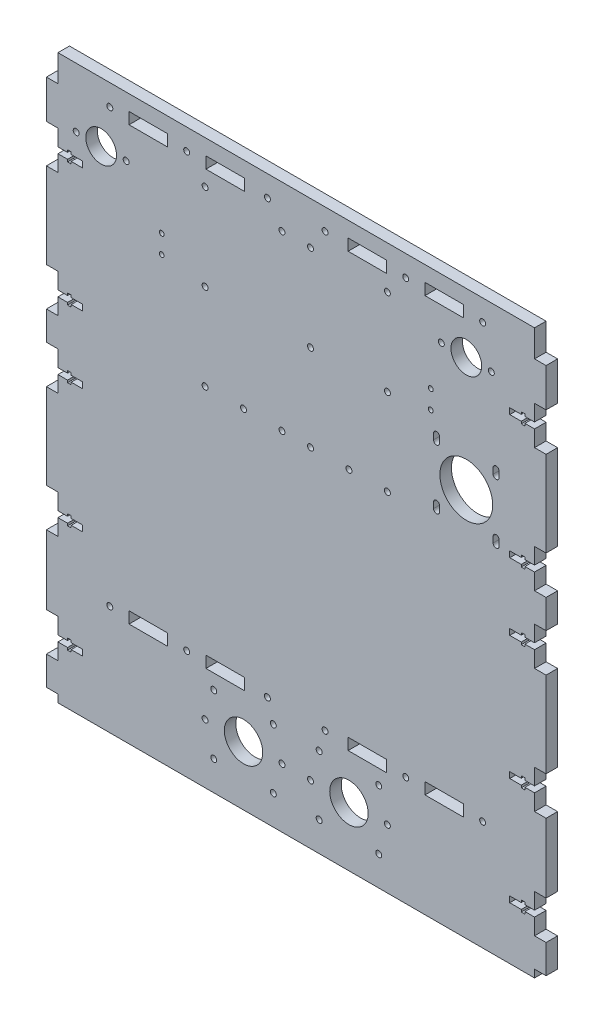
SolidWorks part; units mm, degrees
ref_plane "Front Plane" through (0, 0, 0) normal (0, 0, 1) x (1, 0, 0)
ref_plane "Top Plane" through (0, 0, 0) normal (0, 1, 0) x (1, 0, 0)
ref_plane "Right Plane" through (0, 0, 0) normal (1, 0, 0) x (0, 0, -1)
sketch "Sketch1" plane through (0, 0, 0) normal (0, 0, 1) x (1, 0, 0)
  line L1 (0, 0) -> (260, 0)
  line L2 (0, 0) -> (0, 270)
  line L3 (0, 270) -> (260, 270)
  line L4 (260, 0) -> (260, 270)
  dimension "D1" = 270
  dimension "D2" = 260
extrude "Boss-Extrude1" add sketch "Sketch1" along normal blind 6
sketch "Sketch2" plane through (0, 0, 0) normal (0, 0, -1) x (-1, 0, 0)
  line L0 (-130, 270) -> (-130, 0) construction
  line L1 (-217, 56) -> (-197, 56)
  line L2 (-217, 56) -> (-217, 50)
  line L3 (-217, 50) -> (-197, 50)
  line L4 (-197, 56) -> (-197, 50)
  line L5 (-177, 56) -> (-157, 56)
  line L6 (-177, 56) -> (-177, 50)
  line L7 (-177, 50) -> (-157, 50)
  line L8 (-157, 56) -> (-157, 50)
  line L9 (-260, 270) -> (0, 270) construction
  line L10 (0, 0) -> (-260, 0) construction
  line L11 (-260, 0) -> (-260, 270) construction
  line L12 (-217, 53) -> (-157, 53) construction
  line L13 (-130, 0) -> (-130, -73.8705) construction
  line L14 (-130, -73.8705) -> (-130, -196.098) construction
  line L16 (-220, 0) -> (-40, 0)
  line L17 (-83, 50) -> (-103, 50)
  line L18 (-103, 56) -> (-103, 50)
  line L19 (-83, 56) -> (-103, 56)
  line L20 (-83, 56) -> (-83, 50)
  line L21 (-43, 50) -> (-63, 50)
  line L22 (-63, 56) -> (-63, 50)
  line L23 (-43, 56) -> (-63, 56)
  line L24 (-43, 56) -> (-43, 50)
  arc A0 (-220, 0) -> (-40, 0) centre (-130, -400) cw
  point P23 (-130, 10)
  point P26 (-130, 10)
  dimension "D9" = 40
  dimension "D1" = 43
  dimension "D2" = 20
  dimension "D3" = 20
  dimension "D4" = 20
  dimension "D5" = 6
  dimension "D6" = 6
  dimension "D7" = 50
  dimension "D8" = 3
  dimension "D12" = 10
extrude "Cut-Extrude1" cut sketch "Sketch2" against normal blind 6
sketch "Sketch3" plane through (0, 0, 0) normal (0, 0, -1) x (-1, 0, 0)
  line L2 (-260, 255) -> (-260, 235)
  line L4 (-254, 255) -> (-254, 235)
  line L5 (-197, 56) -> (-217, 56) construction
  line L6 (-260, 255) -> (-254, 255)
  line L7 (-260, 255) -> (-260, 235)
  line L8 (-260, 235) -> (-254, 235)
  line L9 (-254, 255) -> (-254, 235)
  line L10 (-260, 190.5) -> (-254, 190.5)
  line L11 (-260, 190.5) -> (-260, 170.5)
  line L12 (-260, 170.5) -> (-254, 170.5)
  line L13 (-254, 190.5) -> (-254, 170.5)
  line L14 (-254, 155.5) -> (-260, 155.5)
  line L15 (-254, 155.5) -> (-254, 135.5)
  line L16 (-254, 135.5) -> (-260, 135.5)
  line L17 (-260, 155.5) -> (-260, 135.5)
  line L18 (-260, 91) -> (-254, 91)
  line L19 (-260, 91) -> (-260, 71)
  line L20 (-260, 71) -> (-254, 71)
  line L21 (-254, 91) -> (-254, 71)
  line L22 (-260, 35) -> (-254, 35)
  line L23 (-260, 35) -> (-260, 15)
  line L24 (-260, 15) -> (-254, 15)
  line L25 (-254, 35) -> (-254, 15)
  line L27 (-254, 190.5) -> (-254, 170.5)
  line L28 (-260, 190.5) -> (-260, 170.5)
  line L29 (-260, 155.5) -> (-260, 135.5)
  line L30 (-254, 155.5) -> (-254, 135.5)
  line L31 (-254, 91) -> (-254, 71)
  line L32 (-260, 91) -> (-260, 71)
  line L33 (-260, 35) -> (-260, 15)
  line L34 (-254, 35) -> (-254, 15)
  line L35 (-254, 270) -> (-254, 0) construction
  line L36 (-260, 270) -> (0, 270) construction
  line L37 (-220, 0) -> (-260, 0) construction
  line L38 (-260, 0) -> (-260, 270) construction
  line L39 (-130, 270) -> (-130, 0) construction
  line L40 (0, 15) -> (-6, 15)
  line L41 (-6, 35) -> (-6, 15)
  line L42 (0, 35) -> (-6, 35)
  line L43 (0, 35) -> (0, 15)
  line L44 (0, 71) -> (-6, 71)
  line L45 (-6, 91) -> (-6, 71)
  line L46 (0, 91) -> (-6, 91)
  line L47 (0, 91) -> (0, 71)
  line L48 (-6, 135.5) -> (0, 135.5)
  line L49 (0, 155.5) -> (0, 135.5)
  line L50 (-6, 155.5) -> (0, 155.5)
  line L51 (-6, 155.5) -> (-6, 135.5)
  line L52 (0, 170.5) -> (-6, 170.5)
  line L53 (-6, 190.5) -> (-6, 170.5)
  line L54 (0, 190.5) -> (-6, 190.5)
  line L55 (0, 190.5) -> (0, 170.5)
  line L56 (0, 235) -> (-6, 235)
  line L57 (-6, 255) -> (-6, 235)
  line L58 (0, 255) -> (-6, 255)
  line L59 (0, 255) -> (0, 235)
  point P27 (-257, 170.5)
  point P28 (-257, 155.5)
  point P29 (-257, 71)
  line M33 (0, 0) -> (0, 270)
  line M35 (-260, 270) -> (-260, 0)
  dimension "D1" = 6
  dimension "D2" = 20
  dimension "D3" = 20
  dimension "D4" = 20
  dimension "D5" = 20
  dimension "D6" = 20
  dimension "D7" = 6
  dimension "D8" = 15
  dimension "D9" = 44.5
  dimension "D10" = 15
  dimension "D11" = 44.5
extrude "Cut-Extrude2" cut sketch "Sketch3" against normal blind 10 contours L8 L4 L6 M35 | L13 L10 L12 M35 | L16 L15 L14 M35 | L21 L18 L20 M35 | L25 L22 L24 M35 | L42 L41 L40 M33 | L50 L51 L48 M33 | L54 L53 L52 M33 | L58 L57 L56 M33 | L47 L44 L45 L46 region at (257, 245, 0) region at (257, 25, 0) region at (257, 81, 0) region at (257, 145.5, 0) region at (257, 180.5, 0) region at (3, 245, 0) region at (3, 180.5, 0) region at (3, 145.5, 0) region at (3, 25, 0)
sketch "Sketch4" plane through (0, 0, 6) normal (0, 0, 1) x (1, 0, 0)
  line L0 (130, 270) -> (130, 0) construction
  line L1 (260, 270) -> (0, 270) construction
  line L2 (0, 270) -> (0, 255) construction
  line L3 (260, 270) -> (0, 270) construction
  circle A0 centre (28.5, 258) radius 8
  circle A2 centre (218.5, 258) radius 8
  dimension "D1" = 16
  dimension "D4" = 16
  dimension "D2" = 12
  dimension "D3" = 28.5
  dimension "D5" = 190
  dimension "D6" = 12
extrude "Cut-Extrude3" cut sketch "Sketch4" against normal blind 10
sketch "Sketch5" plane through (0, 0, 6) normal (0, 0, 1) x (1, 0, 0)
  line L0 (28.5, 266) -> (28.5, 250) construction
  line L1 (15.5, 258) -> (28.5, 258) construction
  line L2 (130, 270) -> (130, 307.8731) construction
  line L3 (260, 270) -> (0, 270) construction
  line L4 (205.5, 258) -> (231.5, 258) construction
  circle A0 centre (28.5, 258) radius 8 construction
  circle A1 centre (28.5, 258) radius 8
  circle A2 centre (15.5, 258) radius 1.55
  circle A3 centre (41.5, 258) radius 1.55
  circle A7 centre (218.5, 258) radius 8 construction
  circle A8 centre (218.5, 258) radius 8
  circle A9 centre (205.5, 258) radius 1.55
  circle A10 centre (231.5, 258) radius 1.55
  dimension "D2" = 3.1
  dimension "D3" = 3.1
  dimension "D4" = 13
  dimension "D7" = 3.1
  dimension "D1" = 13
  dimension "D5" = 13
  dimension "D6" = 13
extrude "Cut-Extrude4" cut sketch "Sketch5" against normal blind 6
sketch "Sketch6" plane through (0, 270, 0) normal (0, 1, 0) x (1, 0, 0)
  line L4 (260, 0) -> (0, 0)
  line L5 (0, 0) -> (0, -6)
  line L6 (0, -6) -> (260, -6)
  line L7 (260, -6) -> (260, 0)
  line L8 (260, 0) -> (0, 0)
  line L9 (0, 0) -> (0, -6)
  line L10 (0, -6) -> (260, -6)
  line L11 (260, -6) -> (260, 0)
  dimension "D1" = 0
extrude "Boss-Extrude2" add sketch "Sketch6" along normal blind 5
sketch "Sketch7" plane through (0, 0, 6) normal (0, 0, 1) x (1, 0, 0)
  line L0 (203, 212.25) -> (203, 215.25) construction
  line L5 (203, 182.75) -> (234, 182.75) construction
  line L6 (203, 182.75) -> (203, 213.75) construction
  line L9 (203, 213.75) -> (234, 213.75) construction
  line L12 (234, 182.75) -> (234, 213.75) construction
  line L15 (203, 182.75) -> (234, 213.75)
  line L19 (203, 213.75) -> (234, 182.75)
  line L20 (130, 275) -> (130, 247.8561) construction
  line L21 (0, 275) -> (260, 275) construction
  line L24 (201.45, 212.25) -> (201.45, 215.25)
  line L27 (204.55, 212.25) -> (204.55, 215.25)
  line L33 (234, 212.25) -> (234, 215.25) construction
  line L36 (0, 235) -> (0, 190.5) construction
  line L38 (218.5, 213.75) -> (218.5, 146.5893) construction
  line L39 (232.45, 212.25) -> (232.45, 215.25)
  line L40 (235.55, 212.25) -> (235.55, 215.25)
  line L41 (234, 181.25) -> (234, 184.25) construction
  line L42 (232.45, 181.25) -> (232.45, 184.25)
  line L43 (235.55, 181.25) -> (235.55, 184.25)
  line L44 (203, 181.25) -> (203, 184.25) construction
  line L45 (201.45, 181.25) -> (201.45, 184.25)
  line L46 (204.55, 181.25) -> (204.55, 184.25)
  circle A9 centre (28.5, 258) radius 8 construction
  circle A10 centre (28.5, 258) radius 8 construction
  arc A24 (201.45, 212.25) -> (204.55, 212.25) centre (203, 212.25) ccw
  arc A25 (204.55, 215.25) -> (201.45, 215.25) centre (203, 215.25) ccw
  arc A26 (232.45, 212.25) -> (235.55, 212.25) centre (234, 212.25) ccw
  arc A27 (235.55, 215.25) -> (232.45, 215.25) centre (234, 215.25) ccw
  arc A28 (232.45, 181.25) -> (235.55, 181.25) centre (234, 181.25) ccw
  arc A29 (235.55, 184.25) -> (232.45, 184.25) centre (234, 184.25) ccw
  arc A30 (201.45, 181.25) -> (204.55, 181.25) centre (203, 181.25) ccw
  arc A31 (204.55, 184.25) -> (201.45, 184.25) centre (203, 184.25) ccw
  circle A32 centre (218.5, 198.25) radius 13.75
  point P0 (218.5, 198.25)
  point P7 (203, 213.75)
  point P19 (234, 213.75)
  point P26 (234, 182.75)
  point P33 (203, 182.75)
  point P81 (55.5, 184.0856)
  dimension "D1" = 3.1
  dimension "D3" = 31
  dimension "D4" = 31
  dimension "D7" = 27.5
  dimension "D2" = 3
  dimension "D6" = 218.5
  dimension "D5" = 59.75
extrude "Cut-Extrude5" cut sketch "Sketch7" against normal blind 16 contours L19 A32 L15 | L15 A32 L19 | L19 A32 L15 | L15 A32 L19 | L43 A29 L42 A28 | A30 L46 A31 L45 | A24 L27 A25 L24 | A26 L40 A27 L39 region at (210.2471, 198.25, 6) region at (218.5, 189.9971, 6) region at (218.5, 206.5029, 6) region at (226.7529, 198.25, 6)
sketch "Sketch8" plane through (0, 0, 6) normal (0, 0, 1) x (1, 0, 0)
  line L0 (130, 137.5) -> (99.5396, 137.5) construction
  line L1 (0, 275) -> (260, 275) construction
  line L2 (0, 163) -> (24.6988, 163) construction
  line L3 (12.9, 243.45) -> (12.9, 242.25)
  line L4 (0, 170.5) -> (0, 155.5) construction
  line L5 (12.9, 243.45) -> (18.9, 243.45)
  line L6 (0, 113.25) -> (22.1113, 113.25) construction
  line L7 (0, 135.5) -> (0, 91) construction
  line L8 (0, 53) -> (19.2315, 53) construction
  line L9 (0, 71) -> (0, 35) construction
  line L34 (130, 275) -> (130, 0) construction
  line L35 (0, 212.75) -> (26.3273, 212.75) construction
  line L36 (0, 235) -> (0, 190.5) construction
  line L37 (6, 255) -> (6, 235) construction
  line L38 (6, 246.55) -> (11, 246.55)
  line L39 (6, 246.55) -> (6, 243.45)
  line L40 (6, 243.45) -> (11, 243.45)
  line L41 (18.9, 246.55) -> (18.9, 243.45)
  line L42 (6, 245) -> (35.7835, 245) construction
  line L43 (12.9, 246.55) -> (18.9, 246.55)
  line L44 (0, 255) -> (6, 255) construction
  line L45 (11, 243.45) -> (11, 242.25)
  line L46 (11, 247.75) -> (12.9, 247.75)
  line L47 (11, 247.75) -> (11, 246.55)
  line L48 (11, 242.25) -> (12.9, 242.25)
  line L49 (12.9, 247.75) -> (12.9, 246.55)
  line L50 (12.9, 177.75) -> (12.9, 178.95)
  line L51 (11, 183.25) -> (12.9, 183.25)
  line L52 (11, 177.75) -> (11, 178.95)
  line L53 (11, 177.75) -> (12.9, 177.75)
  line L54 (11, 182.05) -> (11, 183.25)
  line L55 (12.9, 178.95) -> (18.9, 178.95)
  line L56 (18.9, 178.95) -> (18.9, 182.05)
  line L57 (6, 182.05) -> (11, 182.05)
  line L58 (6, 178.95) -> (6, 182.05)
  line L59 (6, 178.95) -> (11, 178.95)
  line L60 (12.9, 182.05) -> (18.9, 182.05)
  line L61 (12.9, 182.05) -> (12.9, 183.25)
  line L62 (12.9, 143.95) -> (12.9, 142.75)
  line L63 (12.9, 143.95) -> (18.9, 143.95)
  line L64 (6, 147.05) -> (11, 147.05)
  line L65 (6, 147.05) -> (6, 143.95)
  line L66 (6, 143.95) -> (11, 143.95)
  line L67 (18.9, 147.05) -> (18.9, 143.95)
  line L68 (12.9, 147.05) -> (18.9, 147.05)
  line L69 (11, 143.95) -> (11, 142.75)
  line L70 (11, 148.25) -> (12.9, 148.25)
  line L71 (11, 148.25) -> (11, 147.05)
  line L72 (11, 142.75) -> (12.9, 142.75)
  line L73 (12.9, 148.25) -> (12.9, 147.05)
  line L74 (12.9, 78.25) -> (12.9, 79.45)
  line L75 (11, 83.75) -> (12.9, 83.75)
  line L76 (11, 78.25) -> (11, 79.45)
  line L77 (11, 78.25) -> (12.9, 78.25)
  line L78 (11, 82.55) -> (11, 83.75)
  line L79 (12.9, 79.45) -> (18.9, 79.45)
  line L80 (18.9, 79.45) -> (18.9, 82.55)
  line L81 (6, 82.55) -> (11, 82.55)
  line L82 (6, 79.45) -> (6, 82.55)
  line L83 (6, 79.45) -> (11, 79.45)
  line L84 (12.9, 82.55) -> (18.9, 82.55)
  line L85 (12.9, 82.55) -> (12.9, 83.75)
  line L86 (12.9, 23.45) -> (12.9, 22.25)
  line L87 (12.9, 23.45) -> (18.9, 23.45)
  line L88 (6, 26.55) -> (11, 26.55)
  line L89 (6, 26.55) -> (6, 23.45)
  line L90 (6, 23.45) -> (11, 23.45)
  line L91 (18.9, 26.55) -> (18.9, 23.45)
  line L92 (12.9, 26.55) -> (18.9, 26.55)
  line L93 (11, 23.45) -> (11, 22.25)
  line L94 (11, 27.75) -> (12.9, 27.75)
  line L95 (11, 27.75) -> (11, 26.55)
  line L96 (11, 22.25) -> (12.9, 22.25)
  line L97 (12.9, 27.75) -> (12.9, 26.55)
  line L98 (254, 245) -> (224.2165, 245) construction
  line L99 (260, 212.75) -> (233.6727, 212.75) construction
  line L100 (260, 53) -> (240.7685, 53) construction
  line L101 (260, 113.25) -> (237.8887, 113.25) construction
  line L102 (260, 163) -> (235.3012, 163) construction
  line L103 (247.1, 27.75) -> (247.1, 26.55)
  line L104 (249, 22.25) -> (247.1, 22.25)
  line L105 (249, 27.75) -> (249, 26.55)
  line L106 (249, 27.75) -> (247.1, 27.75)
  line L107 (249, 23.45) -> (249, 22.25)
  line L108 (247.1, 26.55) -> (241.1, 26.55)
  line L109 (241.1, 26.55) -> (241.1, 23.45)
  line L110 (254, 23.45) -> (249, 23.45)
  line L111 (254, 26.55) -> (254, 23.45)
  line L112 (254, 26.55) -> (249, 26.55)
  line L113 (247.1, 23.45) -> (241.1, 23.45)
  line L114 (247.1, 23.45) -> (247.1, 22.25)
  line L115 (247.1, 82.55) -> (247.1, 83.75)
  line L116 (247.1, 82.55) -> (241.1, 82.55)
  line L117 (254, 79.45) -> (249, 79.45)
  line L118 (254, 79.45) -> (254, 82.55)
  line L119 (254, 82.55) -> (249, 82.55)
  line L120 (241.1, 79.45) -> (241.1, 82.55)
  line L121 (247.1, 79.45) -> (241.1, 79.45)
  line L122 (249, 82.55) -> (249, 83.75)
  line L123 (249, 78.25) -> (247.1, 78.25)
  line L124 (249, 78.25) -> (249, 79.45)
  line L125 (249, 83.75) -> (247.1, 83.75)
  line L126 (247.1, 78.25) -> (247.1, 79.45)
  line L127 (247.1, 148.25) -> (247.1, 147.05)
  line L128 (249, 142.75) -> (247.1, 142.75)
  line L129 (249, 148.25) -> (249, 147.05)
  line L130 (249, 148.25) -> (247.1, 148.25)
  line L131 (249, 143.95) -> (249, 142.75)
  line L132 (247.1, 147.05) -> (241.1, 147.05)
  line L133 (241.1, 147.05) -> (241.1, 143.95)
  line L134 (254, 143.95) -> (249, 143.95)
  line L135 (254, 147.05) -> (254, 143.95)
  line L136 (254, 147.05) -> (249, 147.05)
  line L137 (247.1, 143.95) -> (241.1, 143.95)
  line L138 (247.1, 143.95) -> (247.1, 142.75)
  line L139 (247.1, 182.05) -> (247.1, 183.25)
  line L140 (247.1, 182.05) -> (241.1, 182.05)
  line L141 (254, 178.95) -> (249, 178.95)
  line L142 (254, 178.95) -> (254, 182.05)
  line L143 (254, 182.05) -> (249, 182.05)
  line L144 (241.1, 178.95) -> (241.1, 182.05)
  line L145 (247.1, 178.95) -> (241.1, 178.95)
  line L146 (249, 182.05) -> (249, 183.25)
  line L147 (249, 177.75) -> (247.1, 177.75)
  line L148 (249, 177.75) -> (249, 178.95)
  line L149 (249, 183.25) -> (247.1, 183.25)
  line L150 (247.1, 177.75) -> (247.1, 178.95)
  line L151 (247.1, 247.75) -> (247.1, 246.55)
  line L152 (249, 242.25) -> (247.1, 242.25)
  line L153 (249, 247.75) -> (249, 246.55)
  line L154 (249, 247.75) -> (247.1, 247.75)
  line L155 (249, 243.45) -> (249, 242.25)
  line L156 (247.1, 246.55) -> (241.1, 246.55)
  line L157 (241.1, 246.55) -> (241.1, 243.45)
  line L158 (254, 243.45) -> (249, 243.45)
  line L159 (254, 246.55) -> (254, 243.45)
  line L160 (254, 246.55) -> (249, 246.55)
  line L161 (247.1, 243.45) -> (241.1, 243.45)
  line L162 (247.1, 243.45) -> (247.1, 242.25)
  dimension "D1" = 10
  dimension "D2" = 1.55
  dimension "D3" = 12.9
  dimension "D4" = 6
  dimension "D5" = 5
  dimension "D6" = 5.5
  dimension "D7" = 2.75
extrude "Cut-Extrude6" cut sketch "Sketch8" against normal blind 10
sketch "Sketch9" plane through (0, 0, 6) normal (0, 0, 1) x (1, 0, 0)
  line L0 (0, 53) -> (260, 53) construction
  line L1 (0, 71) -> (0, 35) construction
  line L2 (260, 35) -> (260, 71) construction
  line L3 (130, 53) -> (130, 64.3337) construction
  line L4 (43, 50) -> (43, 56) construction
  line L5 (63, 56) -> (63, 50) construction
  circle A0 centre (33, 53) radius 1.55
  circle A1 centre (73, 53) radius 1.55
  circle A2 centre (115, 53) radius 1.55
  circle A3 centre (145, 53) radius 1.55
  circle A4 centre (187, 53) radius 1.55
  circle A5 centre (227, 53) radius 1.55
  dimension "D1" = 3.1
  dimension "D2" = 15
  dimension "D3" = 3.1
  dimension "D4" = 3.1
  dimension "D5" = 10
  dimension "D6" = 10
extrude "Cut-Extrude7" cut sketch "Sketch9" against normal blind 10
sketch "Sketch11" plane through (0, 0, 0) normal (0, 0, 1) x (1, 0, 0)
  line L0 (157.4295, 5) -> (157.4295, 275) construction
  line L1 (157.4295, 5) -> (200, 5) construction
  line L2 (177.4295, 176.8379) -> (177.4295, 178.3879) construction
  line L3 (157.4295, 275) -> (200, 275) construction
  line L4 (157.4295, 176.8379) -> (157.4295, 178.55) construction
  line L5 (200, 5) -> (200, 275) construction
  line L6 (177.4295, 220.2879) -> (177.4295, 223.3879) construction
  line L7 (0, 275) -> (260, 275) construction
  line L8 (177.4302, 26.8379) -> (137.4288, 26.8379) construction
  line L10 (260, 35) -> (260, 71) construction
  line L12 (137.4295, 220.2879) -> (137.4295, 223.3879) construction
  line L13 (137.4295, 176.8379) -> (137.4295, 178.3879) construction
  line L14 (130, 275) -> (130, 282.4006) construction
  line L15 (260, 275) -> (0, 275) construction
  line L16 (122.5705, 176.8379) -> (122.5705, 178.3879) construction
  line L17 (122.5705, 220.2879) -> (122.5705, 223.3879) construction
  line L18 (82.5698, 26.8379) -> (122.5712, 26.8379) construction
  line L19 (82.5705, 220.2879) -> (82.5705, 223.3879) construction
  line L20 (60, 5) -> (60, 275) construction
  line L21 (102.5705, 176.8379) -> (102.5705, 178.55) construction
  line L22 (102.5705, 275) -> (60, 275) construction
  line L23 (82.5705, 176.8379) -> (82.5705, 178.3879) construction
  line L24 (102.5705, 5) -> (60, 5) construction
  line L25 (102.5705, 5) -> (102.5705, 275) construction
  line L26 (260, 255) -> (260, 275) construction
  circle A0 centre (177.4295, 221.8379) radius 1.55
  circle A1 centre (177.4295, 266.8379) radius 1.55
  circle A6 centre (157.4295, 26.8379) radius 10
  circle A7 centre (137.4288, 26.8379) radius 1.55
  circle A8 centre (141.9302, 42.3379) radius 1.55
  circle A9 centre (141.9302, 11.3379) radius 1.55
  circle A10 centre (172.9288, 11.3379) radius 1.55
  circle A14 centre (172.9288, 42.3379) radius 1.55
  circle A15 centre (177.4302, 26.8379) radius 1.55
  circle A17 centre (177.4295, 176.8379) radius 1.55
  circle A18 centre (157.4295, 176.8379) radius 1.55
  circle A20 centre (137.4295, 176.8379) radius 1.55
  circle A21 centre (137.4295, 266.8379) radius 1.55
  circle A22 centre (137.4295, 221.8379) radius 1.55
  circle A37 centre (122.5705, 221.8379) radius 1.55
  circle A38 centre (122.5705, 266.8379) radius 1.55
  circle A39 centre (122.5705, 176.8379) radius 1.55
  circle A40 centre (102.5705, 176.8379) radius 1.55
  circle A41 centre (82.5705, 176.8379) radius 1.55
  circle A42 centre (82.5698, 26.8379) radius 1.55
  circle A43 centre (87.0712, 42.3379) radius 1.55
  circle A44 centre (87.0712, 11.3379) radius 1.55
  circle A45 centre (118.0698, 11.3379) radius 1.55
  circle A46 centre (118.0698, 42.3379) radius 1.55
  circle A47 centre (122.5712, 26.8379) radius 1.55
  circle A48 centre (102.5705, 26.8379) radius 10
  circle A49 centre (82.5705, 266.8379) radius 1.55
  circle A50 centre (82.5705, 221.8379) radius 1.55
  dimension "D3" = 3.1
  dimension "D4" = 3.1
  dimension "D5" = 102.5705
  dimension "D6" = 20
  dimension "D7" = 270
  dimension "D8" = 40
  dimension "D9" = 31
  dimension "D10" = 8.1621
  dimension "D11" = 3.1
  dimension "D12" = 3.1
  dimension "D13" = 3.1
  dimension "D14" = 40.0013
  dimension "D15" = 15.4993
  dimension "D16" = 15.5
  dimension "D17" = 15.4993
  dimension "D18" = 60
  dimension "D21" = 45
  dimension "D23" = 3.1
  dimension "D28" = 3.1
  dimension "D19" = 150
  dimension "D22" = 45
  dimension "D20" = 20
sketch "Sketch12" plane through (0, 0, 0) normal (0, 0, 1) x (1, 0, 0)
  line L0 (130, 270) -> (130, 0) construction
  line L13 (130, 0) -> (130, -73.8705) construction
  line L14 (130, -73.8705) -> (130, -196.098) construction
  line L16 (40, 0) -> (220, 0)
  arc A0 (40, 0) -> (220, 0) centre (130, -400) cw
  point P23 (130, 10)
  point P26 (130, 10)
extrude "Boss-Extrude3" add sketch "Sketch12" along normal blind 6
extrude "Cut-Extrude9" cut sketch "Sketch11" along normal blind 10 contours A6 | A48 | A20 | A22 | A18 | A0 | A17 | A8 | A7 | A9 | A10 | A15 | A14 | A1 | A21 | A40 | A39 | A38 | A41 | A46 | A50 | A49 | A45 | A47 | A43 | A42 | A44 region at (157.4295, 26.8379, 0) region at (102.5705, 26.8379, 0)
sketch "Sketch13" plane through (0, 275, 0) normal (0, 1, 0) x (1, 0, 0)
  line L0 (6, -6) -> (6, 0)
  line L1 (254, 0) -> (254, -6)
  line L2 (0, 0) -> (0, -6) construction
  line L4 (260, -6) -> (260, 0)
  line L5 (260, 0) -> (0, 0)
  line L6 (0, 0) -> (0, -6)
  line L7 (0, -6) -> (260, -6)
  line L9 (254, 0) -> (6, 0)
  line L11 (6, -6) -> (254, -6)
  dimension "D2" = 6
  dimension "D1" = 0
extrude "Boss-Extrude4" add sketch "Sketch13" along normal blind 14
sketch "Sketch14" plane through (0, 0, 0) normal (0, -1, 0) x (1, 0, 0)
  line L0 (6, 6) -> (6, 0)
  line L1 (254, 6) -> (254, 0)
  line L4 (0, 0) -> (260, 0)
  line L5 (260, 0) -> (260, 6)
  line L6 (260, 6) -> (0, 6)
  line L7 (0, 6) -> (0, 0)
  line L8 (6, 0) -> (254, 0)
  line L9 (260, 0) -> (260, 6)
  line L10 (254, 6) -> (6, 6)
  point P8 (260, 3)
  line M5 (0, 0) -> (260, 0)
  line M7 (260, 6) -> (0, 6)
  dimension "D2" = 6
  dimension "D3" = 6
  dimension "D1" = 0
extrude "Boss-Extrude5" add sketch "Sketch14" along normal blind 4 contours L1 L0 M7 M5 region at (130, 0, 3)
sketch "Sketch15" plane through (0, 0, 6) normal (0, 0, 1) x (1, 0, 0)
  line L0 (217, 56) -> (217, 50) construction
  line L1 (217, 50) -> (197, 50) construction
  line L2 (197, 56) -> (217, 56) construction
  line L3 (197, 50) -> (197, 56) construction
  line L4 (177, 50) -> (157, 50) construction
  line L5 (177, 56) -> (177, 50) construction
  line L6 (157, 56) -> (177, 56) construction
  line L7 (157, 50) -> (157, 56) construction
  line L8 (103, 50) -> (83, 50) construction
  line L9 (103, 56) -> (103, 50) construction
  line L10 (83, 56) -> (103, 56) construction
  line L11 (83, 50) -> (83, 56) construction
  line L12 (63, 56) -> (63, 50) construction
  line L13 (63, 50) -> (43, 50) construction
  line L14 (43, 50) -> (43, 56) construction
  line L15 (43, 56) -> (63, 56) construction
  line L16 (217, 56) -> (217, 50)
  line L17 (217, 50) -> (197, 50)
  line L18 (197, 56) -> (217, 56)
  line L19 (197, 50) -> (197, 56)
  line L20 (177, 50) -> (157, 50)
  line L21 (177, 56) -> (177, 50)
  line L22 (157, 56) -> (177, 56)
  line L23 (157, 50) -> (157, 56)
  line L24 (103, 50) -> (83, 50)
  line L25 (103, 56) -> (103, 50)
  line L26 (83, 56) -> (103, 56)
  line L27 (83, 50) -> (83, 56)
  line L28 (63, 56) -> (63, 50)
  line L29 (63, 50) -> (43, 50)
  line L30 (43, 50) -> (43, 56)
  line L31 (43, 56) -> (63, 56)
  line L32 (63, 281) -> (63, 275)
  line L33 (63, 275) -> (43, 275)
  line L34 (43, 275) -> (43, 281)
  line L35 (43, 281) -> (63, 281)
  line L36 (103, 275) -> (83, 275)
  line L37 (83, 275) -> (83, 281)
  line L38 (83, 281) -> (103, 281)
  line L39 (103, 281) -> (103, 275)
  line L40 (177, 275) -> (157, 275)
  line L41 (157, 275) -> (157, 281)
  line L42 (157, 281) -> (177, 281)
  line L43 (177, 281) -> (177, 275)
  line L44 (217, 281) -> (217, 275)
  line L45 (217, 275) -> (197, 275)
  line L46 (197, 275) -> (197, 281)
  line L47 (197, 281) -> (217, 281)
  circle A0 centre (227, 53) radius 1.55 construction
  circle A1 centre (187, 53) radius 1.55 construction
  circle A2 centre (145, 53) radius 1.55 construction
  circle A3 centre (115, 53) radius 1.55 construction
  circle A4 centre (73, 53) radius 1.55 construction
  circle A5 centre (33, 53) radius 1.55 construction
  circle A6 centre (227, 53) radius 1.55
  circle A7 centre (187, 53) radius 1.55
  circle A8 centre (145, 53) radius 1.55
  circle A9 centre (115, 53) radius 1.55
  circle A10 centre (73, 53) radius 1.55
  circle A11 centre (33, 53) radius 1.55
  circle A12 centre (33, 278) radius 1.55
  circle A13 centre (73, 278) radius 1.55
  circle A14 centre (115, 278) radius 1.55
  circle A15 centre (145, 278) radius 1.55
  circle A16 centre (187, 278) radius 1.55
  circle A17 centre (227, 278) radius 1.55
  dimension "D2" = 225
  dimension "D1" = 2
extrude "Cut-Extrude10" cut sketch "Sketch15" against normal blind 10
sketch "Sketch16" plane through (0, 0, 6) normal (0, 0, 1) x (1, 0, 0)
  line L0 (60, 327.3562) -> (60, 187.4877) construction
  line L1 (0, 235) -> (0, 190.5) construction
  line L2 (27.6338, 225) -> (208.8135, 225) construction
  line L3 (6, 289) -> (254, 289) construction
  line L4 (130, 289) -> (130, 298.7127) construction
  line L5 (232.3662, 225) -> (51.1865, 225) construction
  line L6 (200, 327.3562) -> (200, 187.4877) construction
  circle A0 centre (60, 225) radius 1.25
  circle A1 centre (60, 234.6) radius 1.25
  circle A2 centre (200, 234.6) radius 1.25
  circle A3 centre (200, 225) radius 1.25
  point P8 (60, 225)
  dimension "D3" = 2.5
  dimension "D4" = 2.5
  dimension "D5" = 9.6
  dimension "D1" = 60
  dimension "D2" = 64
extrude "Cut-Extrude11" cut sketch "Sketch16" against normal blind 10
